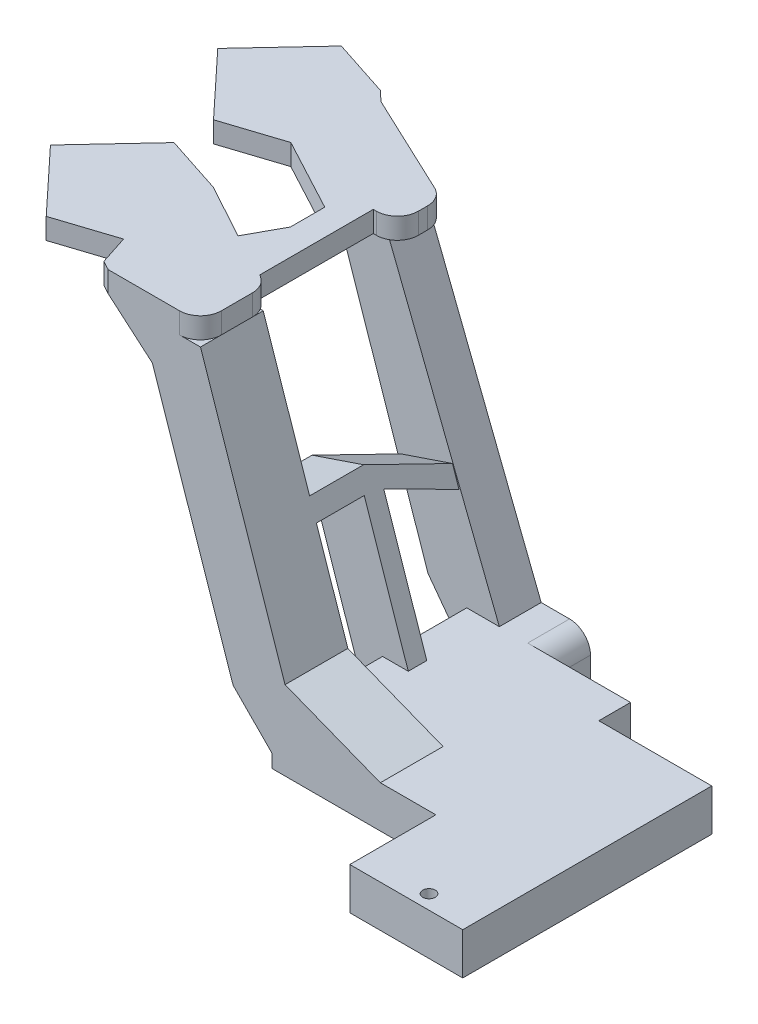
SolidWorks part; units mm, degrees
material "PET"
ref_plane "Alzado" through (0, 0, 0) normal (0, 0, 1) x (1, 0, 0)
ref_plane "Planta" through (0, 0, 0) normal (0, 1, 0) x (1, 0, 0)
ref_plane "Vista lateral" through (0, 0, 0) normal (1, 0, 0) x (0, 0, -1)
sketch "Croquis1" plane through (0, 0, 0) normal (0, 1, 0) x (1, 0, 0)
  line L0 (0, 0) -> (-147.535, 0) construction
  line L2 (-192.3148, 37.3519) -> (-153.15, 37.3519)
  line L6 (-153.15, 37.3519) -> (-153.15, 29.7699)
  line L7 (-153.15, 29.7699) -> (-126.1478, 29.7699)
  line L12 (-126.1478, 29.7699) -> (-126.1478, -29.7699)
  line L17 (-153.15, -29.7699) -> (-126.1478, -29.7699)
  line L19 (-192.3148, -9.1953) -> (-192.3148, 37.3519)
  line L21 (-192.3148, -9.1953) -> (-153.15, -9.1953)
  line L22 (-153.15, -9.1953) -> (-153.15, -29.7699)
  circle A3 centre (-137.6312, -26.3448) radius 1.5
  point P3 (-156.9577, 0.0873)
  point P17 (-126.1478, 0)
  point P22 (-156.9577, -0.0873)
  dimension "D2" = 147.535
extrude "Saliente-Extruir1" add sketch "Croquis1" along normal blind 10
sketch "Croquis3" plane through (0, 0, 9.1953) normal (0, 0, 1) x (1, 0, 0)
  line L0 (-189.1955, 0) -> (-201.6048, 12.5453)
  line L2 (-201.6048, 12.5453) -> (-220.9436, 69.6801)
  line L5 (-209.4336, 78.7242) -> (-189.1955, 18.9327)
  line L6 (-189.1955, 18.9327) -> (-166.4279, 10)
  line L9 (-189.1955, 0) -> (-166.4279, 0)
  line L12 (-166.4279, 10) -> (-166.4279, 0)
  line L13 (-220.9436, 69.6801) -> (-231.4951, 78.7242)
  line L14 (-231.4951, 78.7242) -> (-209.4336, 78.7242)
extrude "Saliente-Extruir2" add sketch "Croquis3" against normal blind 15
sketch "Croquis8" plane through (-163.9984, -55.5098, 0) normal (0.9472, 0.3206, 0) x (0, 0, -1)
  line L0 (5.8047, 102.0234) -> (5.8047, 107.1059)
  line L3 (5.8047, 78.5912) -> (5.8047, 141.7149) construction
  line L5 (5.8047, 102.0234) -> (17.2295, 102.0234)
  line L6 (17.2295, 102.0234) -> (17.2295, 62.1956)
  line L12 (17.2295, 62.1956) -> (21.6494, 62.1956)
  line L14 (21.6494, 101.2355) -> (21.6494, 62.1956)
  line L15 (41.4126, 92.2401) -> (21.6494, 101.2355)
  line L16 (41.4126, 97.1393) -> (41.4126, 92.2401)
  line L17 (41.4126, 97.1393) -> (18.7036, 107.1059)
  line L18 (5.8047, 107.1059) -> (18.7036, 107.1059)
  point P0 (30.6053, 97.1591)
  point P10 (0, 64.6018)
extrude "Saliente-Extruir3" add sketch "Croquis8" against normal blind 13 contours L12 region at (-193.4058, 31.3718, -21.393)
sketch "Croquis10" plane through (0, 78.7242, 0) normal (0, 1, 0) x (1, 0, 0)
  line L0 (-233.72, 49.6957) -> (-261.3301, 49.6957) construction
  line L10 (-249.9187, 64.9725) -> (-235.9805, 60.4311)
  line L11 (-264.1884, 49.6957) -> (-249.9187, 64.9725)
  line L12 (-249.9187, 34.4189) -> (-264.1884, 49.6957)
  line L13 (-235.9805, 38.9603) -> (-249.9187, 34.4189)
  line L15 (-235.9805, 60.4311) -> (-233.72, 58.2162)
  line L18 (-209.4336, -9.1953) -> (-231.4951, -9.1953) construction
  line L40 (-233.72, 58.2162) -> (-209.3805, 46.7405)
  line L42 (-249.9187, 24.9725) -> (-235.9805, 20.4311)
  line L43 (-264.1884, 9.6957) -> (-249.9187, 24.9725)
  line L44 (-249.9187, -5.5811) -> (-264.1884, 9.6957)
  line L45 (-235.9805, -1.0397) -> (-249.9187, -5.5811)
  line L46 (-235.9805, -1.0397) -> (-233.72, -7.9776)
  line L47 (-233.72, -7.9776) -> (-231.4951, -9.1953)
  line L48 (-235.9805, 20.4311) -> (-233.72, 18.2162) [skipped]
  line L49 (-210.5063, 7.2713) -> (-199.5292, 2.0957) [skipped]
  line L52 (-231.4951, 5.8047) -> (-231.4951, -9.1953) construction
  line L53 (-231.4951, -9.1953) -> (-214.4336, -9.1953)
  line L54 (-209.4336, -4.1953) -> (-209.4336, 3.2431)
  line L55 (-211.5126, 7.3012) -> (-212.2737, 7.849)
  line L56 (-212.2737, 7.849) -> (-212.2737, 34.966)
  line L57 (-212.2737, 34.966) -> (-211.5128, 34.966)
  line L58 (-235.9805, 20.4311) -> (-222.9643, 13.3077)
  line L59 (-206.5128, 39.966) -> (-206.5128, 42.218)
  line L63 (-222.9643, 13.3077) -> (-218.5316, 21.4075)
  line L64 (-218.5316, 21.4075) -> (-218.5316, 29.6238)
  line L65 (-218.5316, 29.6238) -> (-235.9805, 38.9603)
  arc A0 (-214.4336, -9.1953) -> (-209.4336, -4.1953) centre (-214.4336, -4.1953) ccw
  arc A1 (-209.4336, 3.2431) -> (-211.5126, 7.3012) centre (-214.4336, 3.2431) ccw
  arc A2 (-211.5128, 34.966) -> (-206.5128, 39.966) centre (-211.5128, 39.966) ccw
  arc A3 (-209.3805, 46.7405) -> (-206.5128, 42.218) centre (-211.5128, 42.218) cw
  point P22 (-239.7162, 6.3979)
  point P27 (-239.7162, 46.3979)
  point P51 (-209.4336, 5.8047)
  dimension "D1" = 2
  dimension "D2" = 5
extrude "Saliente-Extruir7" add sketch "Croquis10" along normal blind 5
fillet "Redondeo2" radius 10 1 edges at (-196.2527, -0.7654, -19.4394)
sketch "Croquis13" plane through (0, 0, -37.3519) normal (0, 0, -1) x (-1, 0, 0)
  line L0 (192.3148, 0) -> (201.6048, 12.5453)
  line L1 (153.15, 0) -> (192.3148, 0) construction
  line L2 (192.3148, 10) -> (192.3148, 0) construction
  line L3 (201.6048, 12.5453) -> (220.9436, 69.6801)
  line L4 (220.9436, 69.6801) -> (201.6048, 12.5453) construction
  line L5 (220.9436, 69.6801) -> (227.2124, 78.1455)
  line L6 (177.7324, 10) -> (184.5153, 10)
  line L7 (153.15, 10) -> (192.3148, 10) construction
  line L8 (184.5153, 10) -> (211.2239, 78.1455)
  line L9 (211.2239, 78.1455) -> (227.2124, 78.1455)
  line L11 (182.7324, 0) -> (192.3148, 0)
  line L12 (172.7324, 5) -> (172.7324, 0)
  line L13 (172.7324, 0) -> (182.7324, 0)
  arc A0 (177.7324, 10) -> (172.7324, 5) centre (177.7324, 5) ccw
  point P20 (172.7324, 10)
  dimension "D1" = 5
extrude "Saliente-Extruir8" add sketch "Croquis13" along normal blind 10
equation "\"80.7.00mm\"=65"
